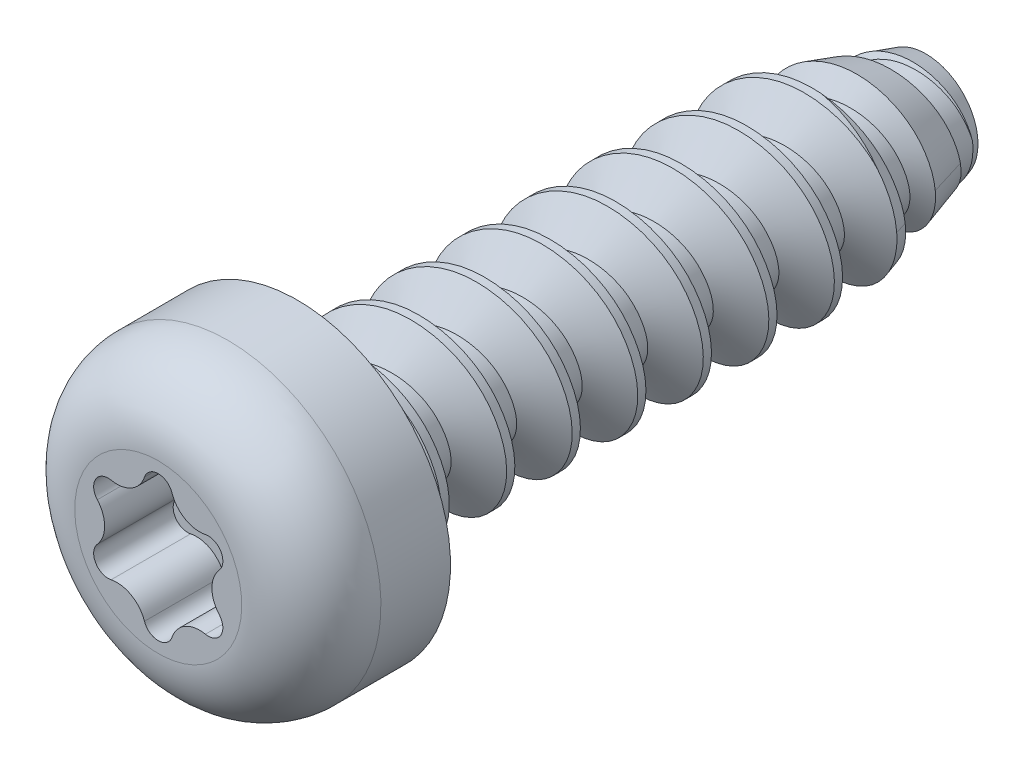
SolidWorks part; units mm, degrees
note: '?' marks a value the reader was unsure of.
ref_plane "Front" through (0, 0, 0) normal (0, 0, 1) x (1, 0, 0)
ref_plane "Top" through (0, 0, 0) normal (0, 1, 0) x (1, 0, 0)
ref_plane "Right" through (0, 0, 0) normal (1, 0, 0) x (0, 0, -1)
sketch "Sketch1" plane through (0, 0, 0) normal (0, 0, 1) x (1, 0, 0)
  circle A0 centre (0, 0) radius 3.41
  dimension "Head Dia" = 6.82
extrude "Extrude3" add sketch "Sketch1" along normal blind 3.1
ref_plane "Plane1" through (0, 0, 3.1) normal (0, 0, 1) x (1, 0, 0)
sketch "Sketch11" plane through (0, 0, 0) normal (1, 0, 0) x (0, 0, -1)
  line L2 (-3.1, 3.41) -> (-3.1, -3.41) construction
  line L4 (0, 3.41) -> (-3.1, 3.41) construction
  line L5 (-1.55, 3.41) -> (-1.55, 3.51)
  line L6 (-1.55, 3.51) -> (-3.2, 3.51)
  line L7 (-3.2, 3.51) -> (-3.2, 1.86)
  line L8 (-3.2, 1.86) -> (-3.1, 1.86)
  line L11 (0, 0) -> (-3.1, 0) construction
  arc A0 (-3.1, 1.86) -> (-1.55, 3.41) centre (-1.55, 1.86) cw
  dimension "D1" = 0.1
  dimension "D2" = 0.1
revolve "Cut-Revolve3" cut sketch "Sketch11" angle 360 about L11
sketch "Sketch14" plane through (0, 0, 0) normal (1, 0, 0) x (0, 0, -1)
  line L0 (0.365, 1.2098) -> (0.8213, 2) construction
  line L2 (0.8213, 2) -> (1.0038, 2)
  line L3 (1.0038, 2) -> (1.46, 1.2098) construction
  line L4 (1.46, 1.2098) -> (0.365, 1.2098) construction
  line L5 (1.46, 1.2098) -> (1.825, 1.2098) construction
  line L6 (0.365, 1.2098) -> (0, 1.2098) construction
  line L10 (0, 3.41) -> (0, -3.41) construction
  line L11 (0.8213, 2) -> (0.365, 1.2098)
  line L12 (0.365, 1.2098) -> (1.46, 1.2098)
  line L13 (1.46, 1.2098) -> (1.0038, 2)
  line L14 (0, 0) -> (-3.1, 0) construction
  line L15 (0, 0) -> (-3.1, 0) construction
  point P11 (0.9125, 2)
  dimension "D1" = 60
  dimension "Pitch" = 1.46
  dimension "D3" = 0.365
  dimension "D4" = 0.1825
  dimension "Screw Dia" = 4
ref_plane "Plane2" through (0, 0, -0.9125) normal (0, 0, 1) x (1, 0, 0)
sketch "Sketch4" plane through (0, 0, 0) normal (1, 0, 0) x (0, 0, -1)
  line L0 (0, 0) -> (14, 0)
  line L2 (14, -1.2098) -> (0, -1.2098) construction
  line L3 (14, 0) -> (14, 1.2098)
  line L4 (14, 1.2098) -> (0, 1.2098)
  line L5 (0, 0) -> (-3.1, 0) construction
  line L6 (0, 1.2098) -> (0, 0)
  line L7 (14, 0) -> (16.54, 0) construction
  line L8 (0.365, 1.2098) -> (1.46, 1.2098) construction
  point P7 (0, 1.2098)
  dimension "Body Length" = 14
  dimension "D1" = 2.54
revolve "Revolve1" add sketch "Sketch4" angle 360 about L7
sketch "Sketch15" plane through (0, 0, -0.9125) normal (0, 0, 1) x (1, 0, 0)
  circle A0 centre (0, 0) radius 2
curve "Helix/Spiral1" pitch 1.46 height 2.19 radius 2 centre (0, 0, -0.9125) axis (0, 0, -1) start towards (0, 1, 0)
sweep "Sweep1" add profiles "Sketch14" path "Helix/Spiral1"
pattern_linear "LPattern3" count 10 spacing 1.46 along (0, 0, -1) count 2 spacing 1.46 along (0, 0, 1) of "Sweep1"
sketch "Sketch13" plane through (0, 0, 0) normal (1, 0, 0) x (0, 0, -1)
  line L0 (14, 1.1598) -> (11.2683, 2)
  line L2 (11.2683, 2) -> (14, 2)
  line L3 (14, 2) -> (14, 1.1598) construction
  line L4 (14, 1.1598) -> (14, 0)
  line L5 (0, 0) -> (14, 0) construction
  line L6 (0.8213, 2) -> (1.0038, 2) construction
  line L7 (16.92, 0) -> (16.92, 2)
  line L8 (16.92, 2) -> (14, 2)
  line L9 (14, 0) -> (16.92, 0)
  dimension "D3" = 2.92
  dimension "D1" = 17.097
  dimension "D2" = 0.05
revolve "Cut-Revolve4" cut sketch "Sketch13" angle 360 about L5
sketch "Sketch12" plane through (0, 0, 3.1) normal (0, 0, 1) x (1, 0, 0)
  line L0 (0, 0) -> (0, 1.6112) construction
  line L1 (-0.5975, 1.035) -> (0, 0)
  line L2 (0, 0) -> (0.5975, 1.035)
  arc A0 (-0.5975, 1.035) -> (-0.3072, 1.3902) centre (-0.9215, 1.5961) ccw
  arc A1 (-0.3072, 1.3902) -> (0.3072, 1.3902) centre (0, 1.2873) cw
  arc A2 (0.3072, 1.3902) -> (0.5975, 1.035) centre (0.9215, 1.5961) ccw
  circle A5 centre (0, 0) radius 1.6112 construction
  dimension "M" = 3.2224
  dimension "D2" = 0.324
  dimension "D3" = 0.6479
  dimension "D1" = 60
ref_axis "Axis1" through (0, 0, 3.1) along (0, 0, -1)?
extrude "Cut-Extrude1" cut sketch "Sketch12" against normal blind 1.7714
pattern_circular "CirPattern1" count 6 every 60 about axis through (0, 0, 0) along (0, 0, 1) of "Cut-Extrude1"
sketch "Sketch16" plane through (0, 0, 0) normal (1, 0, 0) x (0, 0, -1)
  line L0 (14, 2) -> (14, -2) construction
  point P0 (-3.1, 1.86)
  point P1 (0, 3.41)
  point P3 (11.2683, -2)
equation "\"D3@LPattern3\"=\"Pitch@Sketch14\""
equation "\"D1@LPattern3\"=(\"Body Length@Sketch4\"/\"Pitch@Sketch14\")"
equation "\"D1@Cut-Extrude1\"=\"Head Ht@Extrude3\"*2/3.5"
equation "\"D3@Sketch14\" = \"Pitch@Sketch14\"/4"
equation "\"D4@Sketch14\" = \"Pitch@Sketch14\"/8"
equation "\"D4@LPattern3\" = \"D3@LPattern3\""
equation "\"D4@Helix/Spiral1\" = \"Pitch@Sketch14\""
equation "\"D2@Sketch12\" = \"Head Dia@Sketch1\" * .0475"
equation "\"D3@Sketch12\" = \"Head Dia@Sketch1\" * .095"
equation "\"M@Sketch12\" = \"Head Dia@Sketch1\" * 0.4725"
equation "\"D3@Sketch13\" = \"D4@Helix/Spiral1\" * 2"
